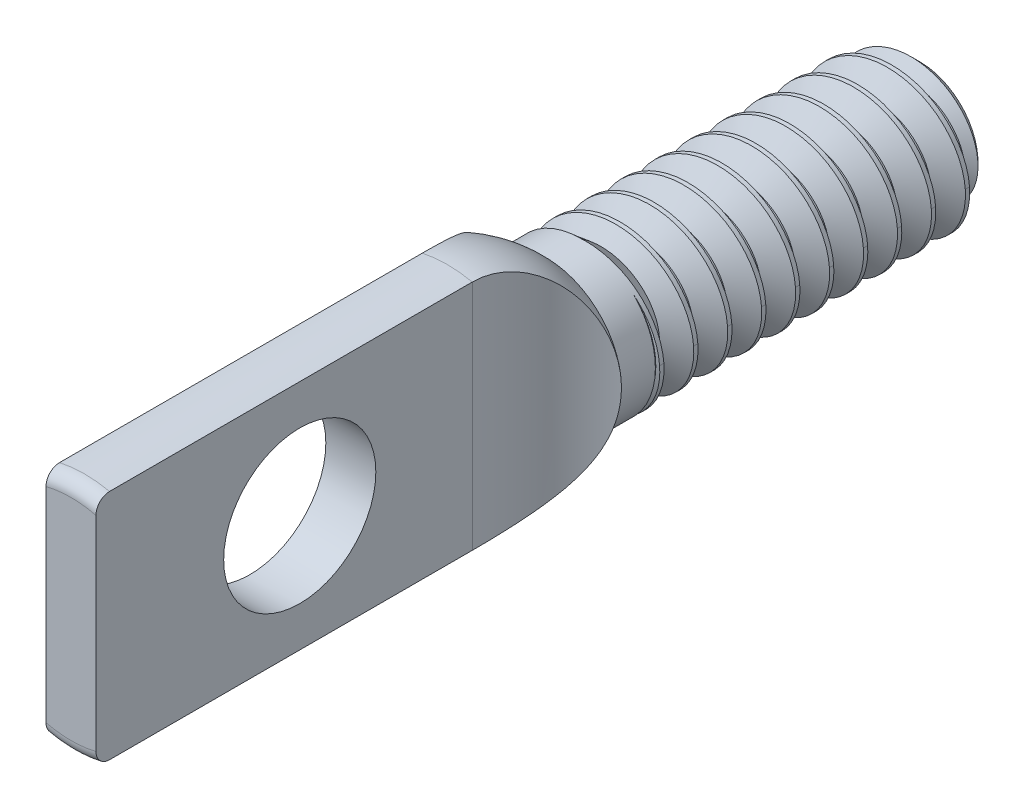
SolidWorks part; units mm, degrees
material "6061-T6 (SS)"
ref_plane "Front Plane" through (0, 0, 0) normal (0, 0, 1) x (1, 0, 0)
ref_plane "Top Plane" through (0, 0, 0) normal (0, 1, 0) x (1, 0, 0)
ref_plane "Right Plane" through (0, 0, 0) normal (1, 0, 0) x (0, 0, -1)
sketch "Sketch1" plane through (0, 0, 0) normal (1, 0, 0) x (0, 0, -1)
  line L0 (6.35, 0) -> (7.1437, 0) construction
  line L1 (-4.7625, 2.7781) -> (6.35, 2.7781)
  line L2 (-4.7625, 2.7781) -> (-4.7625, -2.7781)
  line L3 (-4.7625, -2.7781) -> (6.35, -2.7781)
  line L4 (6.35, 2.7781) -> (6.35, -2.7781)
  line L5 (-4.7625, 2.7781) -> (6.35, -2.7781) construction
  line L6 (-4.7625, -2.7781) -> (6.35, 2.7781) construction
  line L7 (7.1437, 0) -> (15.0812, 0) construction
  line L8 (15.0812, 1.7526) -> (15.0812, -1.7526) construction
  line L9 (15.0316, 1.8385) -> (15.8254, 1.8385) construction
  line L10 (15.8254, 1.8385) -> (15.4285, 1.1511) construction
  line L11 (15.4285, 1.1511) -> (15.4285, 1.237) construction
  line L12 (15.0316, 1.8385) -> (15.4285, 1.1511) construction
  line L13 (15.0812, 1.7526) -> (15.7758, 1.7526) construction
  line L14 (15.3789, 1.237) -> (15.4781, 1.237) construction
  line L15 (15.0564, 1.7956) -> (15.8006, 1.7956) construction
  line L16 (15.4285, 1.7526) -> (15.4285, 1.8385) construction
  line L17 (15.0812, -1.7526) -> (13.0969, -1.7526) construction
  line L18 (7.1437, 0) -> (7.1437, 1.7526) construction
  circle A0 centre (0, 0) radius 1.778
  point P3 (0.7937, 0)
  point P14 (15.0812, 0)
  point P21 (15.4285, 1.7526)
  point P24 (15.4285, 1.237)
  point P27 (15.4285, 1.7956)
  dimension "D1" = 60
  dimension "D2" = 0.0992
  dimension "D3" = 1.9844
sketch "Sketch2" plane through (0, 0, 0) normal (0, 0, 1) x (1, 0, 0)
  line L0 (-0.5842, 0) -> (0.5842, 0) construction
  point P3 (0, 0)
  dimension "Head Thickness (J)" = 1.1684
sketch "Sketch3" plane through (0, 0, 0) normal (1, 0, 0) x (0, 0, -1)
  line L0 (15.0812, 0) -> (15.0812, 1.3557)
  line L1 (14.6844, 1.7526) -> (6.35, 1.7526)
  line L2 (6.35, 2.7781) -> (6.35, -2.7781) construction
  line L4 (4.0326, 2.7781) -> (-4.445, 2.7781)
  line L5 (-4.7625, 2.4606) -> (-4.7625, 0)
  line L6 (-4.7625, 2.7781) -> (-4.7625, -2.7781) construction
  line L7 (-4.7625, 0) -> (15.0812, 0)
  line L8 (15.0812, 1.3557) -> (14.6844, 1.7526)
  arc A0 (6.35, 1.7526) -> (4.0326, 2.7781) centre (4.0326, -0.353) ccw
  arc A1 (6.35, 1.7526) -> (7.1437, 0) centre (4.0326, -0.353) cw construction
  arc A2 (-4.7625, 2.4606) -> (-4.445, 2.7781) centre (-4.445, 2.4606) cw
  point P1 (15.0812, 1.7526)
  point P21 (-4.7625, 2.7781)
  dimension "D3" = 0.3175
  dimension "D1" = 0.3969
  dimension "D2" = 45
revolve "Body Revolve" add sketch "Sketch3" angle 360 about L7
sketch "Sketch5" plane through (0, 0, 0) normal (0, 1, 0) x (1, 0, 0)
  line L0 (0, 0) -> (0, -4.7625) construction
  line L1 (-2.4606, -4.7625) -> (2.4606, -4.7625) construction
  line L2 (-3.3623, 6.35) -> (-3.3623, -4.7625)
  line L3 (-3.3623, -4.7625) -> (-0.5842, -4.7625)
  line L4 (-0.5842, -4.7625) -> (-0.5842, 4.0326)
  line L5 (-1.7526, 6.35) -> (-3.3623, 6.35)
  line L6 (-0.5842, 0) -> (0.5842, 0) construction
  line L8 (1.7526, 6.35) -> (-1.7526, 6.35) construction
  line L9 (1.7526, 6.35) -> (3.3623, 6.35)
  line L10 (0.5842, -4.7625) -> (0.5842, 4.0326)
  line L11 (3.3623, -4.7625) -> (0.5842, -4.7625)
  line L12 (3.3623, 6.35) -> (3.3623, -4.7625)
  arc A0 (-0.5842, 4.0326) -> (-1.7526, 6.35) centre (-3.4666, 4.0326) ccw
  arc A1 (0.5842, 4.0326) -> (1.7526, 6.35) centre (3.4666, 4.0326) cw
  point P19 (-0.5842, 0)
  point P28 (0.5842, 0)
  dimension "D1" = 2.7781
extrude "Head Cut" cut sketch "Sketch5" against normal through all both and the other way through all
sketch "Sketch6" plane through (0, 0, 0) normal (1, 0, 0) x (0, 0, -1)
  circle A1 centre (0, 0) radius 1.778
  circle A2 centre (0, 0) radius 1.778
  dimension "D1" = 0
extrude "Hole Cut" cut sketch "Sketch6" against normal through all both and the other way through all
ref_axis "Center Axis 1" through (0, 0, -31.4706) along (0, 0, 1)
ref_axis "Center Axis 2" through (-0.5842, 0, 0) along (1, 0, 0)
ref_plane "Contact Plane 1" through (0, 0, -7.1437) normal (0, 0, 1) x (1, 0, 0)
ref_plane "Split Plane" through (0, 0, -7.1437) normal (0, 0, 1) x (1, 0, 0)
split "Split1" trim tools "Split Plane" bodies to split 106 resulting bodies 107 108
sketch "Sketch7" plane through (0, 0, -15.0812) normal (0, 0, -1) x (-1, 0, 0)
  circle A0 centre (0, 0) radius 1.7526 construction
  circle A1 centre (0, 0) radius 1.7526
curve "Helix/Spiral1" pitch 0.7937 height 8.7312 radius 1.7526 centre (0, 0, -15.0812) axis (0, 0, 1) start towards (0, 1, 0)
sketch "Sketch8" plane through (0, 0, 0) normal (1, 0, 0) x (0, 0, -1)
  line L0 (15.0564, 1.7956) -> (15.8006, 1.7956)
  line L1 (15.8006, 1.7956) -> (15.4781, 1.237)
  line L2 (15.4781, 1.237) -> (15.3789, 1.237)
  line L3 (15.3789, 1.237) -> (15.0564, 1.7956)
sweep "Thread Cut Sweep" cut profiles "Sketch8" path "Helix/Spiral1" align with end faces yes
sketch "Sketch9" plane through (0, 0, -7.1437) normal (0, 0, 1) x (1, 0, 0)
  circle A1 centre (0, 0) radius 1.7526
  circle A2 centre (0, 0) radius 1.7526
  dimension "D1" = 0
extrude "Thread Extrude" add sketch "Sketch9" against normal through all draft 40
equation "\"D2@Sketch1\"=\"Pitch@Sketch1\"/8"
equation "\"D1@Sketch3\"=\"Pitch@Sketch1\" / 2"
equation "\"D1@Sketch5\"=\"Head Width (H)@Sketch1\"/2"
equation "\"D3@Helix/Spiral1\"=\"Thread Length (B)@Sketch1\"+\"Pitch@Sketch1\""
equation "\"D4@Helix/Spiral1\"=\"Pitch@Sketch1\""
equation "\"D3@Sketch1\"=\"Pitch@Sketch1\"*2.5"
